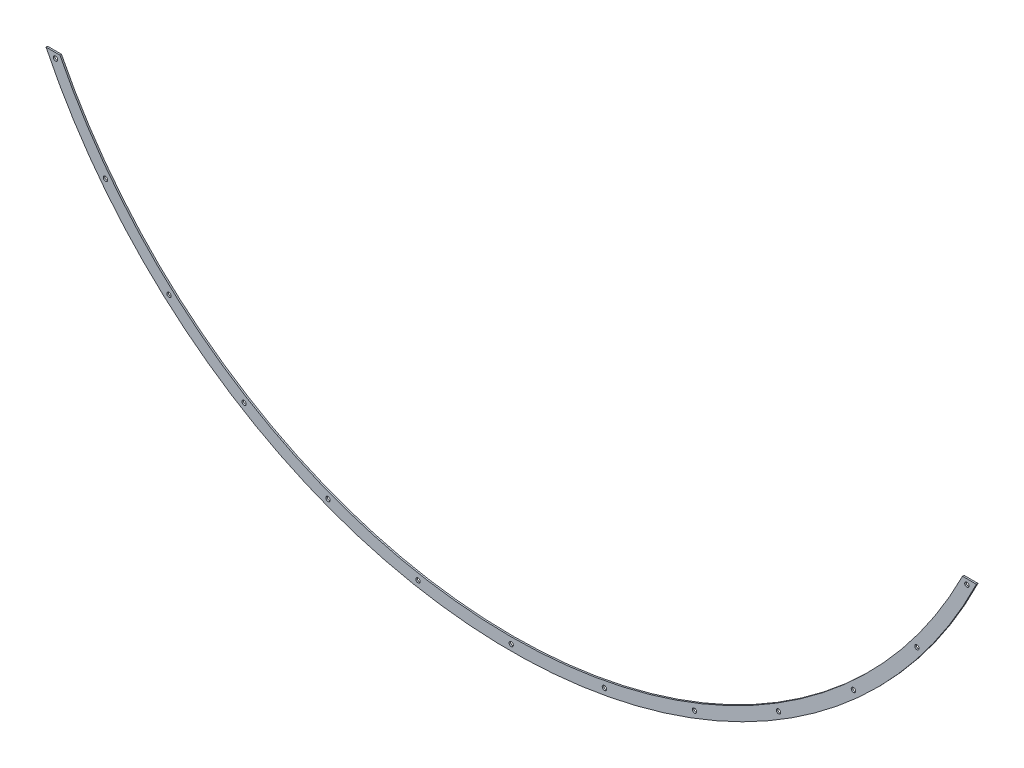
SolidWorks part; units mm, degrees
note: The reader was unsure of these and kept them because the rebuilt part matched: thickness of "Base-Flange1", "Sheet-Metal3", "Sheet-Metal4", "Sheet-Metal8", "Sheet-Metal9", "Sheet-Metal10".
material "AISI 304"
ref_plane "Front Plane" through (0, 0, 0) normal (0, 0, 1) x (1, 0, 0)
ref_plane "Top Plane" through (0, 0, 0) normal (0, 1, 0) x (1, 0, 0)
ref_plane "Right Plane" through (0, 0, 0) normal (1, 0, 0) x (0, 0, -1)
sketch "Sketch1" plane through (0, 0, 0) normal (0, 0, 1) x (1, 0, 0)
  line L0 (829.9849, -5) -> (-829.9849, -5)
  arc A0 (-829.9849, -5) -> (829.9849, -5) centre (0, 0) ccw
  dimension "D1" = 1660
  dimension "D2" = 5
base flange "Base-Flange1" sketch "Sketch1" thickness 2.5 reverse thickness direction no parameters "D1"=0
sketch "Sketch2" plane through (0, 0, 0) normal (0, 0, 1) x (1, 0, 0)
  line L1 (-973.8714, 418.1233) -> (994.6473, 418.1233)
  line L2 (-973.8714, 418.1233) -> (-973.8714, -364)
  line L3 (-973.8714, -364) -> (994.6473, -364)
  line L4 (994.6473, 418.1233) -> (994.6473, -364)
  dimension "D1" = 364
extrude "Cut-Extrude1" cut sketch "Sketch2" against normal blind 10 normal cut yes
sketch "Sketch9" plane through (0, 0, 0) normal (0, 0, 1) x (1, 0, 0)
  line L0 (-723.6049, -364) -> (723.6049, -364)
  line L1 (-745.9249, -364) -> (745.9249, -364) construction
  arc A0 (-723.6049, -364) -> (723.6049, -364) centre (0, 0) ccw
  dimension "D1" = 1620
extrude "Cut-Extrude3" cut sketch "Sketch9" against normal blind 10 normal cut yes
sketch "Sketch10" plane through (0, 0, -2.5) normal (0, 0, -1) x (-1, 0, 0)
  circle A0 centre (0, -820) radius 3.5
  dimension "D1" = 7
  dimension "D2" = 820
extrude "Cut-Extrude4" cut sketch "Sketch10" against normal blind 10 normal cut yes
pattern_circular "CirPattern1" count 10 every 10.5 about axis through (0, 0, 0) along (0, 0, 1) of "Cut-Extrude4"
sketch "Bend-Lines1" [suppressed] plane through (0, 0, 0) normal (0, 1, 0) x (1, 0, 0)
sketch "Bounding-Box1" [suppressed] plane through (0, 0, 0) normal (0, 1, 0) x (1, 0, 0)
sheet metal parameters "Sheet-Metal3" thickness 2.5 parameters "D1"=0
flat pattern "Flat-Pattern3" [suppressed]
sketch "Bend-Lines2" plane through (0, 0, 0) normal (0, 1, 0) x (1, 0, 0)
sketch3d "Bounding-Box2" [suppressed]
  line L0 (789.9842, -5, 0) -> (-789.9842, -5, 0) construction
  line L1 (789.9842, -789.9999, 0) -> (-789.9842, -789.9999, 0) construction
  line L2 (789.9842, -5, 0) -> (789.9842, -789.9999, 0) construction
  line L3 (-789.9842, -5, 0) -> (-789.9842, -789.9999, 0) construction
sheet metal parameters "Sheet-Metal4" thickness 2.5 parameters "D1"=0, "D7"=6
flat pattern "Flat-Pattern3" [suppressed]
sketch "Bend-Lines2" plane through (0, 0, 0) normal (0, 1, 0) x (1, 0, 0)
sketch3d "Bounding-Box2" [suppressed]
  line L0 (-757.0363, -840, 0) -> (757.0363, -840, 0) construction
  line L1 (-757.0363, -364, 0) -> (757.0363, -364, 0) construction
  line L2 (-757.0363, -840, 0) -> (-757.0363, -364, 0) construction
  line L3 (757.0363, -840, 0) -> (757.0363, -364, 0) construction
sketch "Sketch3-1" [suppressed] plane through (0, 0, -2) normal (0, 0, -1) x (-1, 0, 0)
  line L0 (-742.0363, -364) -> (742.0363, -364)
  arc A0 (-742.0363, -364) -> (742.0363, -364) centre (0, 7.863) ccw
  dimension "D3" = 830
  dimension "D1" = 15
  dimension "D2" = 15
sheet metal parameters "Sheet-Metal8" thickness 2.5 parameters "D1"=0, "D7"=6
flat pattern "Flat-Pattern3"
sketch "Bend-Lines2" plane through (0, 0, 0) normal (0, 1, 0) x (1, 0, 0)
sketch3d "Bounding-Box2" [suppressed]
  line L0 (-745.9249, -830, 0) -> (745.9249, -830, 0) construction
  line L1 (-745.9249, -364, 0) -> (745.9249, -364, 0) construction
  line L2 (-745.9249, -830, 0) -> (-745.9249, -364, 0) construction
  line L3 (745.9249, -830, 0) -> (745.9249, -364, 0) construction
sheet metal parameters "Sheet-Metal9" thickness 2.5 parameters "D1"=0, "D7"=6
flat pattern "Flat-Pattern3"
sketch "Bend-Lines2" plane through (0, 0, 0) normal (0, 1, 0) x (1, 0, 0)
sketch3d "Bounding-Box2" [suppressed]
  line L0 (-745.9249, -830, 0) -> (745.9249, -830, 0) construction
  line L1 (-745.9249, -364, 0) -> (745.9249, -364, 0) construction
  line L2 (-745.9249, -830, 0) -> (-745.9249, -364, 0) construction
  line L3 (745.9249, -830, 0) -> (745.9249, -364, 0) construction
sheet metal parameters "Sheet-Metal10" thickness 2.5 parameters "D1"=0, "D7"=6
flat pattern "Flat-Pattern3"
sketch "Bend-Lines2" plane through (0, 0, 0) normal (0, 1, 0) x (1, 0, 0)
sketch3d "Bounding-Box2" [suppressed]
  line L0 (-745.9249, -830, 0) -> (745.9249, -830, 0) construction
  line L1 (-745.9249, -364, 0) -> (745.9249, -364, 0) construction
  line L2 (-745.9249, -830, 0) -> (-745.9249, -364, 0) construction
  line L3 (745.9249, -830, 0) -> (745.9249, -364, 0) construction
